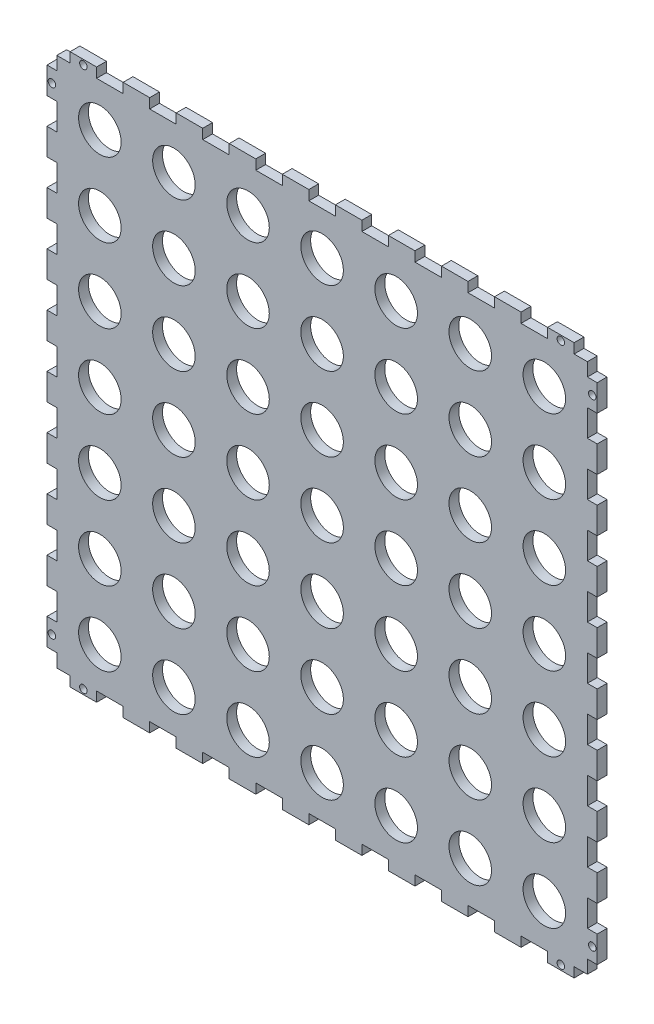
SolidWorks part; units mm, degrees
ref_plane "Front Plane" through (0, 0, 0) normal (0, 0, 1) x (1, 0, 0)
ref_plane "Top Plane" through (0, 0, 0) normal (0, 1, 0) x (1, 0, 0)
ref_plane "Right Plane" through (0, 0, 0) normal (1, 0, 0) x (0, 0, -1)
sketch "Model" plane through (0, 0, 0) normal (0, 0, 1) x (1, 0, 0)
  line L0 (-349.25, 5.6) -> (-349.25, -350) construction
  line L1 (6.35, 5.6) -> (-349.25, 5.6) construction
  line L2 (6.35, -350) -> (6.35, 5.6) construction
  line L3 (-349.25, -350) -> (6.35, -350) construction
  line L4 (-349.25, -350) -> (6.35, 5.6) construction
  line L5 (-350, -172.2) -> (5.6, -172.2) construction
  line L6 (-171.45, -172.581) -> (-171.45, 55.4884) construction
  line L7 (-349.25, -0.75) -> (0, -0.75) construction
  line L8 (-342.9, -343.65) -> (-342.9, 5.6) construction
  line L9 (-349.25, -343.65) -> (0, -343.65) construction
  line L10 (0, -350) -> (0, 5.6) construction
  line L11 (-342.9, -0.75) -> (-334.3275, -0.75)
  line L12 (-334.3275, -0.75) -> (-334.3275, 5.6)
  line L13 (-334.3275, 5.6) -> (-317.1825, 5.6)
  line L14 (-317.1825, 5.6) -> (-317.1825, -0.75)
  line L15 (-317.1825, -0.75) -> (-300.0375, -0.75)
  line L16 (-300.0375, -0.75) -> (-300.0375, 5.6)
  line L17 (-300.0375, 5.6) -> (-282.8925, 5.6)
  line L18 (-282.8925, 5.6) -> (-282.8925, -0.75)
  line L19 (-282.8925, -0.75) -> (-265.7475, -0.75)
  line L20 (-265.7475, -0.75) -> (-265.7475, 5.6)
  line L21 (-265.7475, 5.6) -> (-248.6025, 5.6)
  line L22 (-248.6025, 5.6) -> (-248.6025, -0.75)
  line L23 (-248.6025, -0.75) -> (-231.4575, -0.75)
  line L24 (-231.4575, -0.75) -> (-231.4575, 5.6)
  line L25 (-231.4575, 5.6) -> (-214.3125, 5.6)
  line L26 (-214.3125, 5.6) -> (-214.3125, -0.75)
  line L27 (-214.3125, -0.75) -> (-197.1675, -0.75)
  line L28 (-197.1675, -0.75) -> (-197.1675, 5.6)
  line L29 (-197.1675, 5.6) -> (-180.0225, 5.6)
  line L30 (-180.0225, 5.6) -> (-180.0225, -0.75)
  line L31 (-180.0225, -0.75) -> (-162.8775, -0.75)
  line L32 (-162.8775, -0.75) -> (-162.8775, 5.6)
  line L33 (-162.8775, 5.6) -> (-145.7325, 5.6)
  line L34 (-145.7325, 5.6) -> (-145.7325, -0.75)
  line L35 (-145.7325, -0.75) -> (-128.5875, -0.75)
  line L36 (-128.5875, -0.75) -> (-128.5875, 5.6)
  line L37 (-128.5875, 5.6) -> (-111.4425, 5.6)
  line L38 (-111.4425, 5.6) -> (-111.4425, -0.75)
  line L39 (-111.4425, -0.75) -> (-94.2975, -0.75)
  line L40 (-94.2975, -0.75) -> (-94.2975, 5.6)
  line L41 (-94.2975, 5.6) -> (-77.1525, 5.6)
  line L42 (-77.1525, 5.6) -> (-77.1525, -0.75)
  line L43 (-77.1525, -0.75) -> (-60.0075, -0.75)
  line L44 (-60.0075, -0.75) -> (-60.0075, 5.6)
  line L45 (-60.0075, 5.6) -> (-42.8625, 5.6)
  line L46 (-42.8625, 5.6) -> (-42.8625, -0.75)
  line L47 (-42.8625, -0.75) -> (-25.7175, -0.75)
  line L48 (-25.7175, -0.75) -> (-25.7175, 5.6)
  line L49 (-25.7175, 5.6) -> (-8.5725, 5.6)
  line L50 (-8.5725, 5.6) -> (-8.5725, -0.75)
  line L51 (-8.5725, -0.75) -> (0, -0.75)
  line L52 (-342.9, -0.75) -> (-342.9, -9.3225)
  line L53 (-342.9, -9.3225) -> (-349.25, -9.3225)
  line L54 (-349.25, -9.3225) -> (-349.25, -26.4675)
  line L55 (-349.25, -26.4675) -> (-342.9, -26.4675)
  line L56 (-342.9, -26.4675) -> (-342.9, -43.6125)
  line L57 (-342.9, -43.6125) -> (-349.25, -43.6125)
  line L58 (-349.25, -43.6125) -> (-349.25, -60.7575)
  line L59 (-349.25, -60.7575) -> (-342.9, -60.7575)
  line L60 (-342.9, -60.7575) -> (-342.9, -77.9025)
  line L61 (-342.9, -77.9025) -> (-349.25, -77.9025)
  line L62 (-349.25, -77.9025) -> (-349.25, -95.0475)
  line L63 (-349.25, -95.0475) -> (-342.9, -95.0475)
  line L64 (-342.9, -95.0475) -> (-342.9, -112.1925)
  line L65 (-342.9, -112.1925) -> (-349.25, -112.1925)
  line L66 (-349.25, -112.1925) -> (-349.25, -129.3375)
  line L67 (-349.25, -129.3375) -> (-342.9, -129.3375)
  line L68 (-342.9, -129.3375) -> (-342.9, -146.4825)
  line L69 (-342.9, -146.4825) -> (-349.25, -146.4825)
  line L70 (-349.25, -146.4825) -> (-349.25, -163.6275)
  line L71 (-349.25, -163.6275) -> (-342.9, -163.6275)
  line L72 (-342.9, -163.6275) -> (-342.9, -180.7725)
  line L73 (-342.9, -180.7725) -> (-349.25, -180.7725)
  line L74 (-349.25, -180.7725) -> (-349.25, -197.9175)
  line L75 (-349.25, -197.9175) -> (-342.9, -197.9175)
  line L76 (-342.9, -197.9175) -> (-342.9, -215.0625)
  line L77 (-342.9, -215.0625) -> (-349.25, -215.0625)
  line L78 (-349.25, -215.0625) -> (-349.25, -232.2075)
  line L79 (-349.25, -232.2075) -> (-342.9, -232.2075)
  line L80 (-342.9, -232.2075) -> (-342.9, -249.3525)
  line L81 (-342.9, -249.3525) -> (-349.25, -249.3525)
  line L82 (-349.25, -249.3525) -> (-349.25, -266.4975)
  line L83 (-349.25, -266.4975) -> (-342.9, -266.4975)
  line L84 (-342.9, -266.4975) -> (-342.9, -283.6425)
  line L85 (-342.9, -283.6425) -> (-349.25, -283.6425)
  line L86 (-349.25, -283.6425) -> (-349.25, -300.7875)
  line L87 (-349.25, -300.7875) -> (-342.9, -300.7875)
  line L88 (-342.9, -300.7875) -> (-342.9, -317.9325)
  line L89 (-342.9, -317.9325) -> (-349.25, -317.9325)
  line L90 (-349.25, -317.9325) -> (-349.25, -335.0775)
  line L91 (-349.25, -335.0775) -> (-342.9, -335.0775)
  line L92 (-342.9, -335.0775) -> (-342.9, -343.65)
  line L93 (-342.9, -343.65) -> (-334.3275, -343.65)
  line L94 (-334.3275, -343.65) -> (-334.3275, -350)
  line L95 (-334.3275, -350) -> (-317.1825, -350)
  line L96 (-317.1825, -350) -> (-317.1825, -343.65)
  line L97 (-317.1825, -343.65) -> (-300.0375, -343.65)
  line L98 (-282.8925, -343.65) -> (-265.7475, -343.65)
  line L99 (-282.8925, -350) -> (-282.8925, -343.65)
  line L100 (-300.0375, -350) -> (-282.8925, -350)
  line L101 (-300.0375, -343.65) -> (-300.0375, -350)
  line L102 (-248.6025, -343.65) -> (-231.4575, -343.65)
  line L103 (-248.6025, -350) -> (-248.6025, -343.65)
  line L104 (-265.7475, -350) -> (-248.6025, -350)
  line L105 (-265.7475, -343.65) -> (-265.7475, -350)
  line L106 (-214.3125, -343.65) -> (-197.1675, -343.65)
  line L107 (-214.3125, -350) -> (-214.3125, -343.65)
  line L108 (-231.4575, -350) -> (-214.3125, -350)
  line L109 (-231.4575, -343.65) -> (-231.4575, -350)
  line L110 (-180.0225, -343.65) -> (-162.8775, -343.65)
  line L111 (-180.0225, -350) -> (-180.0225, -343.65)
  line L112 (-197.1675, -350) -> (-180.0225, -350)
  line L113 (-197.1675, -343.65) -> (-197.1675, -350)
  line L114 (-145.7325, -343.65) -> (-128.5875, -343.65)
  line L115 (-145.7325, -350) -> (-145.7325, -343.65)
  line L116 (-162.8775, -350) -> (-145.7325, -350)
  line L117 (-162.8775, -343.65) -> (-162.8775, -350)
  line L118 (-111.4425, -343.65) -> (-94.2975, -343.65)
  line L119 (-111.4425, -350) -> (-111.4425, -343.65)
  line L120 (-128.5875, -350) -> (-111.4425, -350)
  line L121 (-128.5875, -343.65) -> (-128.5875, -350)
  line L122 (-77.1525, -343.65) -> (-60.0075, -343.65)
  line L123 (-77.1525, -350) -> (-77.1525, -343.65)
  line L124 (-94.2975, -350) -> (-77.1525, -350)
  line L125 (-94.2975, -343.65) -> (-94.2975, -350)
  line L126 (-42.8625, -343.65) -> (-25.7175, -343.65)
  line L127 (-42.8625, -350) -> (-42.8625, -343.65)
  line L128 (-60.0075, -350) -> (-42.8625, -350)
  line L129 (-60.0075, -343.65) -> (-60.0075, -350)
  line L130 (-8.5725, -343.65) -> (0, -343.65)
  line L131 (-8.5725, -350) -> (-8.5725, -343.65)
  line L132 (-25.7175, -350) -> (-8.5725, -350)
  line L133 (-25.7175, -343.65) -> (-25.7175, -350)
  line L134 (0, -343.65) -> (0, -335.0775)
  line L135 (0, -335.0775) -> (6.35, -335.0775)
  line L136 (6.35, -335.0775) -> (6.35, -317.9325)
  line L137 (6.35, -317.9325) -> (0, -317.9325)
  line L138 (0, -317.9325) -> (0, -300.7875)
  line L139 (0, -283.6425) -> (0, -266.4975)
  line L140 (6.35, -283.6425) -> (0, -283.6425)
  line L141 (6.35, -300.7875) -> (6.35, -283.6425)
  line L142 (0, -300.7875) -> (6.35, -300.7875)
  line L143 (0, -249.3525) -> (0, -232.2075)
  line L144 (6.35, -249.3525) -> (0, -249.3525)
  line L145 (6.35, -266.4975) -> (6.35, -249.3525)
  line L146 (0, -266.4975) -> (6.35, -266.4975)
  line L147 (0, -215.0625) -> (0, -197.9175)
  line L148 (6.35, -215.0625) -> (0, -215.0625)
  line L149 (6.35, -232.2075) -> (6.35, -215.0625)
  line L150 (0, -232.2075) -> (6.35, -232.2075)
  line L151 (0, -180.7725) -> (0, -163.6275)
  line L152 (6.35, -180.7725) -> (0, -180.7725)
  line L153 (6.35, -197.9175) -> (6.35, -180.7725)
  line L154 (0, -197.9175) -> (6.35, -197.9175)
  line L155 (0, -146.4825) -> (0, -129.3375)
  line L156 (6.35, -146.4825) -> (0, -146.4825)
  line L157 (6.35, -163.6275) -> (6.35, -146.4825)
  line L158 (0, -163.6275) -> (6.35, -163.6275)
  line L159 (0, -112.1925) -> (0, -95.0475)
  line L160 (6.35, -112.1925) -> (0, -112.1925)
  line L161 (6.35, -129.3375) -> (6.35, -112.1925)
  line L162 (0, -129.3375) -> (6.35, -129.3375)
  line L163 (0, -77.9025) -> (0, -60.7575)
  line L164 (6.35, -77.9025) -> (0, -77.9025)
  line L165 (6.35, -95.0475) -> (6.35, -77.9025)
  line L166 (0, -95.0475) -> (6.35, -95.0475)
  line L167 (0, -43.6125) -> (0, -26.4675)
  line L168 (6.35, -43.6125) -> (0, -43.6125)
  line L169 (6.35, -60.7575) -> (6.35, -43.6125)
  line L170 (0, -60.7575) -> (6.35, -60.7575)
  line L171 (0, -0.75) -> (0, -9.3225)
  line L172 (6.35, -9.3225) -> (0, -9.3225)
  line L173 (6.35, -26.4675) -> (6.35, -9.3225)
  line L174 (0, -26.4675) -> (6.35, -26.4675)
  line L175 (0, -9.3225) -> (0, 5.6) [skipped]
  circle A0 centre (-267.208, -28.563) radius 13.75
  circle A1 centre (-219.329, -28.563) radius 13.75
  circle A2 centre (-171.45, -28.563) radius 13.75
  circle A3 centre (-123.571, -28.563) radius 13.75
  circle A4 centre (-75.692, -28.563) radius 13.75
  circle A5 centre (-27.813, -28.563) radius 13.75
  circle A6 centre (-267.208, -76.569) radius 13.75
  circle A7 centre (-219.329, -76.569) radius 13.75
  circle A8 centre (-171.45, -76.569) radius 13.75
  circle A9 centre (-123.571, -76.569) radius 13.75
  circle A10 centre (-75.692, -76.569) radius 13.75
  circle A11 centre (-27.813, -76.569) radius 13.75
  circle A12 centre (-267.208, -124.575) radius 13.75
  circle A13 centre (-219.329, -124.575) radius 13.75
  circle A14 centre (-171.45, -124.575) radius 13.75
  circle A15 centre (-123.571, -124.575) radius 13.75
  circle A16 centre (-75.692, -124.575) radius 13.75
  circle A17 centre (-27.813, -124.575) radius 13.75
  circle A18 centre (-267.208, -172.581) radius 13.75
  circle A19 centre (-219.329, -172.581) radius 13.75
  circle A20 centre (-171.45, -172.581) radius 13.75
  circle A21 centre (-123.571, -172.581) radius 13.75
  circle A22 centre (-75.692, -172.581) radius 13.75
  circle A23 centre (-27.813, -172.581) radius 13.75
  circle A24 centre (-267.208, -220.587) radius 13.75
  circle A25 centre (-219.329, -220.587) radius 13.75
  circle A26 centre (-171.45, -220.587) radius 13.75
  circle A27 centre (-123.571, -220.587) radius 13.75
  circle A28 centre (-75.692, -220.587) radius 13.75
  circle A29 centre (-27.813, -220.587) radius 13.75
  circle A30 centre (-267.208, -268.593) radius 13.75
  circle A31 centre (-219.329, -268.593) radius 13.75
  circle A32 centre (-171.45, -268.593) radius 13.75
  circle A33 centre (-123.571, -268.593) radius 13.75
  circle A34 centre (-75.692, -268.593) radius 13.75
  circle A35 centre (-27.813, -268.593) radius 13.75
  circle A36 centre (-267.208, -316.599) radius 13.75
  circle A37 centre (-219.329, -316.599) radius 13.75
  circle A38 centre (-171.45, -316.599) radius 13.75
  circle A39 centre (-123.571, -316.599) radius 13.75
  circle A40 centre (-75.692, -316.599) radius 13.75
  circle A41 centre (-27.813, -316.599) radius 13.75
  circle A42 centre (-315.087, -76.569) radius 13.75
  circle A43 centre (-315.087, -124.575) radius 13.75
  circle A44 centre (-315.087, -172.581) radius 13.75
  circle A45 centre (-315.087, -220.587) radius 13.75
  circle A46 centre (-315.087, -268.593) radius 13.75
  circle A47 centre (-315.087, -316.599) radius 13.75
  circle A48 centre (-325.755, -346.825) radius 2.413
  circle A49 centre (-346.075, -326.505) radius 2.413
  circle A50 centre (-346.075, -17.895) radius 2.413
  circle A51 centre (-325.755, 2.425) radius 2.413
  circle A52 centre (-17.145, -346.825) radius 2.413
  circle A53 centre (3.175, -326.505) radius 2.413
  circle A54 centre (3.175, -17.895) radius 2.413
  circle A55 centre (-17.145, 2.425) radius 2.413
  circle A162 centre (-315.087, -28.563) radius 13.75
  dimension "D3" = 27.5
  dimension "D8" = 4.826
  dimension "D9" = 8.5725
  dimension "D10" = 3.175
  dimension "D2" = 355.6
  dimension "D4" = 34.163
  dimension "D5" = 34.163
  dimension "D11" = 6.35
  dimension "D12" = 6.35
  dimension "D13" = 6.35
  dimension "D14" = 6.35
  dimension "D15" = 8.5725
  dimension "D16" = 17.145
  dimension "D17" = 17.145
  dimension "D6" = 7
  dimension "D7" = 7
  dimension "D18" = 10
  dimension "D19" = 10
  dimension "D20" = 10
  dimension "D21" = 10
extrude "Boss-Extrude2" add sketch "Model" along normal blind 6.35
